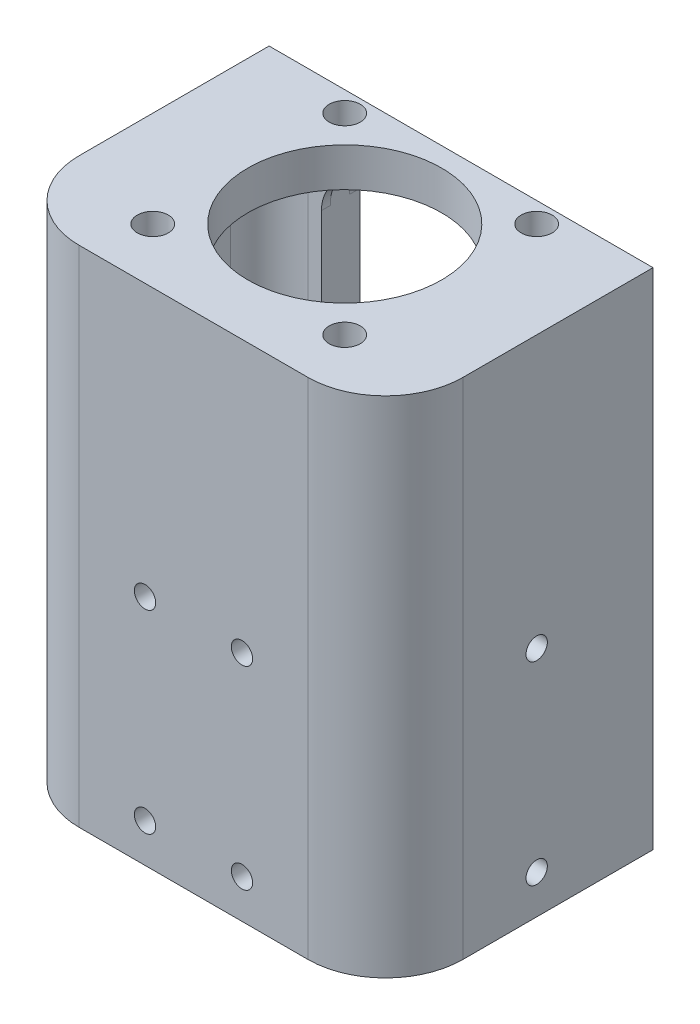
SolidWorks part; units mm, degrees
ref_plane "Front Plane" through (0, 0, 0) normal (0, 0, 1) x (1, 0, 0)
ref_plane "Top Plane" through (0, 0, 0) normal (0, 1, 0) x (1, 0, 0)
ref_plane "Right Plane" through (0, 0, 0) normal (1, 0, 0) x (0, 0, -1)
sketch "Sketch2" plane through (0, 0, 0) normal (0, 1, 0) x (1, 0, 0)
  line L1 (-39.5, -29) -> (39.5, -29) construction
  line L2 (-39.5, -29) -> (-39.5, 29) construction
  line L3 (-39.5, 29) -> (39.5, 29) construction
  line L4 (39.5, -29) -> (39.5, 29) construction
  line L5 (-39.5, -29) -> (39.5, 29) construction
  line L6 (-39.5, 29) -> (39.5, -29) construction
  line L7 (-49.5, 30) -> (49.5, 30)
  line L8 (-49.5, 30) -> (-49.5, -39)
  line L9 (-49.5, -39) -> (49.5, -39)
  line L10 (49.5, 30) -> (49.5, -39)
  circle A0 centre (0, 0) radius 25
  point P0 (0, 0)
  point P10 (0, 30)
  dimension "D5" = 50
  dimension "D1" = 58
  dimension "D2" = 79
  dimension "D3" = 10
  dimension "D4" = 10
  dimension "D6" = 30
extrude "Boss-Extrude1" add sketch "Sketch2" along normal blind 10
sketch "Sketch3" plane through (0, 0, 0) normal (0, -1, 0) x (1, 0, 0)
  line L0 (-49.5, -30) -> (-49.5, 39)
  line L1 (-49.5, 39) -> (49.5, 39)
  line L2 (49.5, 39) -> (49.5, -30)
  line L3 (49.5, -30) -> (39.5, -30)
  line L4 (-49.5, -30) -> (49.5, -30) construction
  line L5 (39.5, -30) -> (39.5, 29)
  line L6 (39.5, 29) -> (-39.5, 29)
  line L7 (-39.5, 29) -> (-39.5, -30)
  line L8 (-39.5, -30) -> (-49.5, -30)
  line L9 (39.5, 29) -> (39.5, -29) construction
extrude "Boss-Extrude2" add sketch "Sketch3" along normal blind 120
hole_wizard "CBORE for M5 SHCS1" positions "Sketch4" profile "Sketch5" counterbore size "M5" standard "ANSI Metric" end condition through all
sketch "Sketch4" plane through (0, 10, 0) normal (0, 1, 0) x (1, 0, 0)
  line L1 (-24.7487, 24.7487) -> (24.7487, 24.7487)
  line L2 (-24.7487, 24.7487) -> (-24.7487, -24.7487)
  line L3 (-24.7487, -24.7487) -> (24.7487, -24.7487)
  line L4 (24.7487, 24.7487) -> (24.7487, -24.7487)
  circle A0 centre (0, 0) radius 35
  point P5 (-24.7487, 24.7487)
  point P6 (24.7487, -24.7487)
  point P91 (-24.7487, -24.7487)
  point P92 (24.7487, 24.7487)
  dimension "D1" = 70
sketch "Sketch5" plane through (24.7487, 10, -24.7487) normal (1, 0, 0) x (0, 0, 1)
  line L0 (0, 0) -> (0, 130)
  line L1 (0, 130) -> (2.75, 130)
  line L3 (2.75, 130) -> (2.75, 7)
  line L4 (2.75, 7) -> (4, 7)
  line L5 (4, 7) -> (4, 0)
  line L7 (4, 0) -> (0, 0)
  line L11 (0, -6.35) -> (0, 107.95) construction
  dimension "Thru Hole Dia." = 5.5
  dimension "Thru Hole Depth" = 130
  dimension "C'Bore Dia." = 8
  dimension "C'Bore Depth" = 7
hole_wizard "M5 Clearance Hole1" positions "Sketch6" profile "Sketch8" hole size "M5" standard "ANSI Metric" end condition through all
sketch "Sketch6" plane through (0, 0, 39) normal (0, 0, 1) x (1, 0, 0)
  line L1 (-12.5, -60) -> (12.5, -60)
  line L2 (-12.5, -60) -> (-12.5, -110)
  line L3 (-12.5, -110) -> (12.5, -110)
  line L4 (12.5, -60) -> (12.5, -110)
  point P9 (-12.5, -60)
  point P10 (12.5, -110)
  point P79 (-12.5, -110)
  point P80 (12.5, -60)
  point P92 (0, -60)
  dimension "D1" = 25
  dimension "D2" = 60
  dimension "D3" = 50
sketch "Sketch8" plane through (-12.5, -60, 39) normal (1, 0, 0) x (0, -1, 0)
  line L0 (0, 0) -> (0, 69)
  line L1 (0, 69) -> (2.75, 69)
  line L2 (2.75, 69) -> (2.75, 0)
  line L5 (2.75, 0) -> (0, 0)
  line L11 (0, -6.35) -> (0, 107.95) construction
  dimension "Thru Hole Dia." = 5.5
  dimension "Thru Hole Depth" = 69
hole_wizard "M5 Clearance Hole2" positions "Sketch9" profile "Sketch10" hole size "M5" standard "ANSI Metric" end condition up to next
sketch "Sketch9" plane through (49.5, 0, 0) normal (1, 0, 0) x (0, 0, -1)
  line L0 (-39, -107.25) -> (-39, -112.75) construction
  line L1 (-39, -57.25) -> (-39, -62.75) construction
  line L2 (-39, -107.25) -> (-39, -112.75)
  line L3 (-39, -57.25) -> (-39, -62.75)
  point P0 (0, -60)
  point P2 (0, -110)
  point P9 (0, 0)
  point P10 (-39, -60)
  point P11 (0, 0)
  point P12 (-39, -110)
sketch "Sketch10" plane through (49.5, -60, 0) normal (0, 1, 0) x (0, 0, -1)
  line L0 (0, 0) -> (0, 10)
  line L1 (0, 10) -> (2.75, 10)
  line L2 (2.75, 10) -> (2.75, 0)
  line L5 (2.75, 0) -> (0, 0)
  line L11 (0, -6.35) -> (0, 107.95) construction
  dimension "Thru Hole Dia." = 5.5
  dimension "Thru Hole Depth" = 10
sketch "Sketch11" plane through (-39.5, 0, 0) normal (1, 0, 0) x (0, 0, -1)
  line L0 (30, 0) -> (-29, 0) construction
  line L1 (20, 0) -> (30, 0)
  line L2 (20, 0) -> (20, -120)
  line L3 (20, -120) -> (30, -120)
  line L4 (30, 0) -> (30, -120)
  dimension "D1" = 10
extrude "Boss-Extrude3" add sketch "Sketch11" along normal blind 13.5
fillet "Fillet1" radius 20 2 edges at (-49.5, -55, 39) (49.5, -55, 39)
fillet "Fillet2" radius 10 6 edges at (39.5, 0, -0.5) (-39.5, 0, 4.5) (-39.5, -60, 29) (39.5, -60, 29) (-26, 0, -28.5988) (-39.5, -60, -20)
